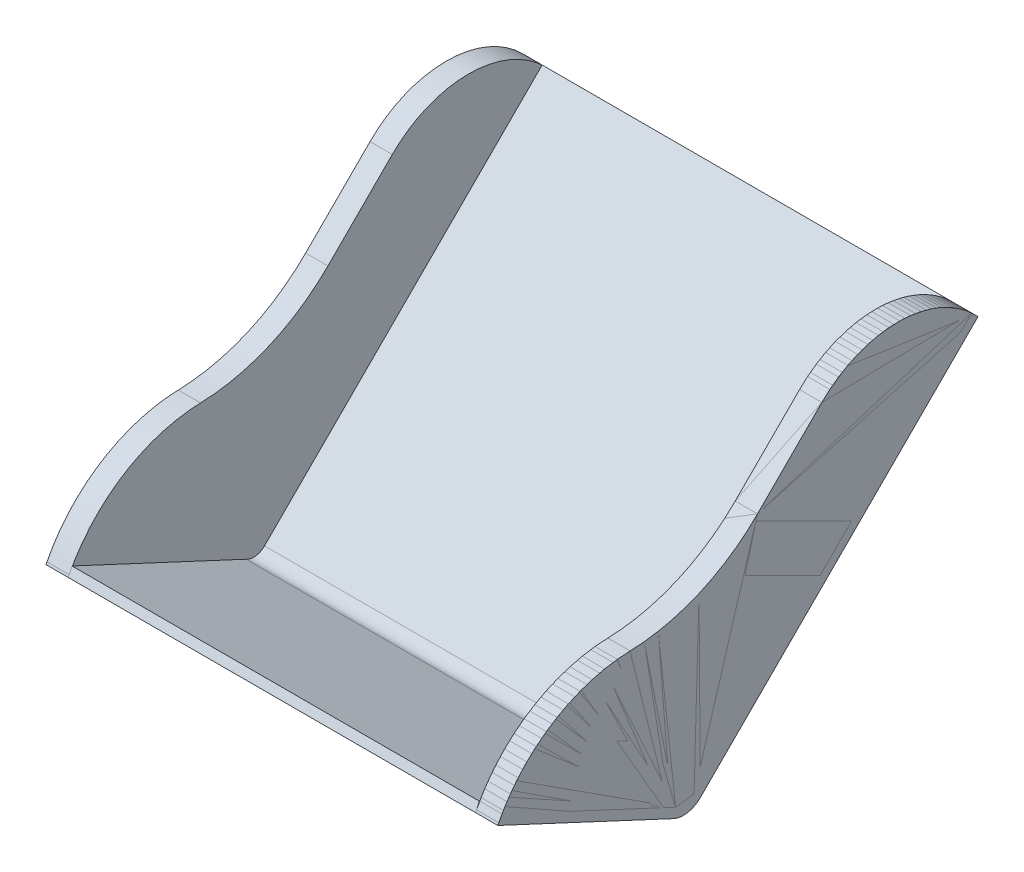
SolidWorks part; units mm, degrees
ref_plane "Front Plane" through (0, 0, 0) normal (0, 0, 1) x (1, 0, 0)
ref_plane "Top Plane" through (0, 0, 0) normal (0, 1, 0) x (1, 0, 0)
ref_plane "Right Plane" through (0, 0, 0) normal (1, 0, 0) x (0, 0, -1)
sketch "Sketch2" plane through (0, 0, 0) normal (1, 0, 0) x (0, 0, -1)
  line L0 (11.6057, 11.6057) -> (323.2892, 323.2892)
  line L1 (-20.8577, 7.2143) -> (-215.7656, 98.1013)
  arc A0 (-20.8577, 7.2143) -> (11.6057, 11.6057) centre (-7.5087, 30.7202) ccw
  point P5 (-3.885, 3.9323)
  dimension "D1" = 110
  dimension "D2" = 457.2
  dimension "D3" = 584.2
  dimension "D4" = 231.8646
extrude "Extrude-Thin2" add sketch "Sketch2" along normal mid plane 457.2 thin thin type one direction wall 10
sketch "Sketch3" plane through (228.6, 0, 0) normal (1, 0, 0) x (0, 0, -1)
  line L0 (11.6057, 11.6057) -> (323.2892, 323.2892)
  line L1 (323.2892, 323.2892) -> (319.0685, 327.51)
  line L2 (147.9812, 327.51) -> (75.7393, 255.2681)
  line L3 (-157.9792, 211.1508) -> (-158.1705, 211.2345)
  line L4 (-214.6825, 100.2289) -> (-215.7656, 98.1013)
  line L5 (-215.7656, 98.1013) -> (-20.8577, 7.2143)
  arc A0 (-67.2962, 193.5639) -> (75.7393, 255.2681) centre (-73.4439, 404.4513) ccw
  arc A1 (147.9812, 327.51) -> (319.0685, 327.51) centre (233.5248, 241.9663) cw
  arc A2 (-214.6825, 100.2289) -> (-67.2962, 193.5639) centre (-62.314, 22.6595) cw
  arc A3 (-20.8577, 7.2143) -> (11.6057, 11.6057) centre (-7.5087, 30.7202) ccw
  line M5 (-16.2263, 16.0884) -> (-211.5394, 107.1644)
  line M7 (-215.7656, 98.1013) -> (-20.8577, 7.2143)
  arc M8 (-20.8577, 7.2143) -> (11.6057, 11.6057) centre (-7.5087, 30.7202) ccw
  line M9 (11.6057, 11.6057) -> (323.2892, 323.2892)
  line M10 (323.2892, 323.2892) -> (316.2182, 330.3603)
  line M11 (316.2182, 330.3603) -> (4.5347, 18.6768)
  arc M12 (4.5347, 18.6768) -> (-16.2263, 16.0884) centre (-7.5087, 30.7202) cw
  dimension "D4" = 210.977
  dimension "D2" = 120.977
  dimension "D3" = 170.977
  dimension "D1" = 126.946
extrude "Boss-Extrude1" add sketch "Sketch3" along normal blind 25 separate body contours A2 A1 L2 A0 M5 M12 M11 region at (228.6, 182.0831, -52.2502)
extrude "Boss-Extrude2" add sketch "Sketch3<3>" along normal blind 25 separate body contours A2 L4 A1 M7 M8 M9 M10 M11 M12 M5 | A2 A1 L2 A0 M5 M12 M11 region at (228.6, 10.1783, 4.7299) region at (228.6, 182.0831, -52.2502)
sketch "Sketch3<3>" plane through (228.6, 0, 0) normal (1, 0, 0) x (0, 0, -1) same geometry as "Sketch3"
mirror "Mirror11" about plane through (0, 0, 0) normal (1, 0, 0) of bodies 104
